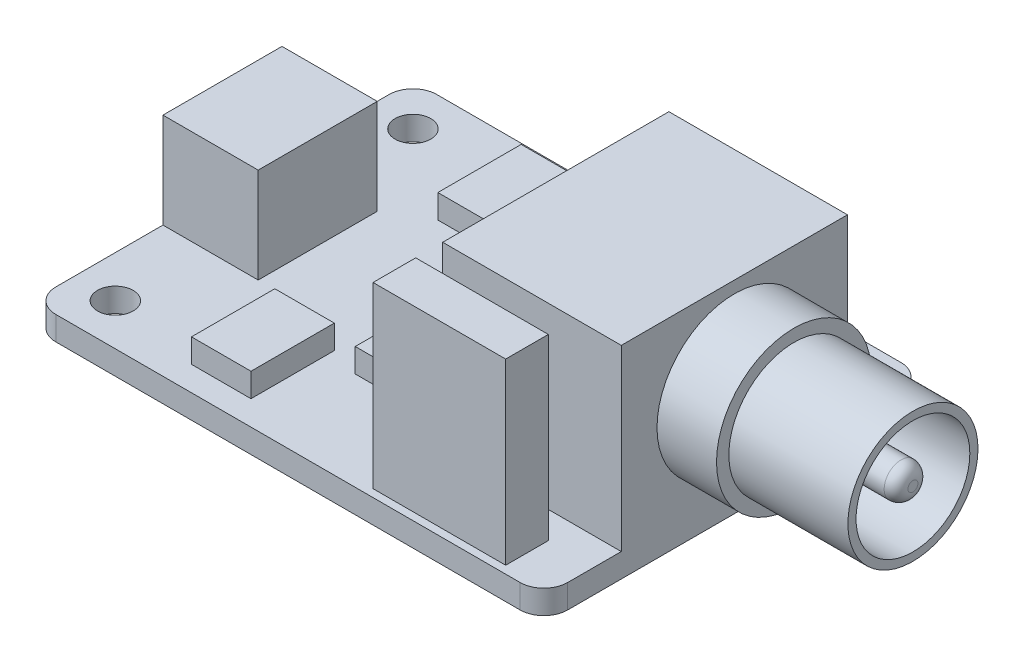
SolidWorks part; units mm, degrees
ref_plane "Front Plane" through (0, 0, 0) normal (0, 0, 1) x (1, 0, 0)
ref_plane "Top Plane" through (0, 0, 0) normal (0, 1, 0) x (1, 0, 0)
ref_plane "Right Plane" through (0, 0, 0) normal (1, 0, 0) x (0, 0, -1)
sketch "Sketch1" plane through (0, 0, 0) normal (0, 1, 0) x (1, 0, 0)
  line L1 (-179.1905, 78.9286) -> (-136.1905, 78.9286)
  line L2 (-179.1905, 78.9286) -> (-179.1905, 46.9286)
  line L3 (-179.1905, 46.9286) -> (-136.1905, 46.9286)
  line L4 (-136.1905, 78.9286) -> (-136.1905, 46.9286)
  circle A0 centre (-175.6905, 75.4286) radius 1.5
  circle A1 centre (-175.6905, 50.4286) radius 1.5
  dimension "D3" = 3
  dimension "D4" = 3
  dimension "D7" = 3.5
  dimension "D8" = 3.5
  dimension "D9" = 3.5
  dimension "D10" = 3.5
  dimension "D1" = 43
  dimension "D2" = 32
extrude "Boss-Extrude1" add sketch "Sketch1" along normal blind 2
fillet "Fillet1" radius 2 4 edges at (-179.1905, 1, -78.9286) (-136.1905, 1, -78.9286) (-136.1905, 1, -46.9286) (-179.1905, 1, -46.9286)
sketch "Sketch2" plane through (0, 2, 0) normal (0, 1, 0) x (1, 0, 0)
  line L0 (-179.1905, 76.9286) -> (-179.1905, 48.9286) construction
  line L1 (-195.986, 57.9286) -> (-187.986, 57.9286)
  line L2 (-195.986, 57.9286) -> (-195.986, 67.9286)
  line L3 (-195.986, 67.9286) -> (-187.986, 67.9286)
  line L4 (-187.986, 57.9286) -> (-187.986, 67.9286)
  line L6 (-151.1905, 53.4286) -> (-136.1905, 53.4286)
  line L7 (-151.1905, 53.4286) -> (-151.1905, 72.4286)
  line L8 (-151.1905, 72.4286) -> (-136.1905, 72.4286)
  line L9 (-136.1905, 53.4286) -> (-136.1905, 72.4286)
  line L10 (-136.1905, 48.9286) -> (-136.1905, 76.9286) construction
  line L11 (-177.1905, 46.9286) -> (-138.1905, 46.9286) construction
  line L12 (-138.1905, 78.9286) -> (-177.1905, 78.9286) construction
  line L14 (-151.1905, 51.1605) -> (-140.0499, 51.1605)
  line L15 (-151.1905, 51.1605) -> (-151.1905, 47.5777)
  line L16 (-151.1905, 47.5777) -> (-140.0499, 47.5777)
  line L17 (-140.0499, 51.1605) -> (-140.0499, 47.5777)
  point P4 (-195.986, 62.9286)
  point P7 (-179.1905, 62.9286)
  line M14 (-136.1905, 48.9286) -> (-136.1905, 76.9286)
  dimension "D1" = 10
  dimension "D2" = 8
  dimension "D4" = 15
  dimension "D5" = 6.5
  dimension "D6" = 6.5
extrude "Boss-Extrude2" add sketch "Sketch2" along normal blind 15 contours L8 L7 L6 M14 | L17 L14 L15 L16 region at (-143.6905, 2, -62.9286) region at (-145.6202, 2, -49.3691)
sketch "Sketch3" plane through (0, 2, 0) normal (0, 1, 0) x (1, 0, 0)
  line L0 (-179.1905, 76.9286) -> (-179.1905, 48.9286) construction
  line L1 (-171.1905, 57.9286) -> (-179.1905, 57.9286)
  line L2 (-171.1905, 57.9286) -> (-171.1905, 67.9286)
  line L3 (-171.1905, 67.9286) -> (-179.1905, 67.9286)
  line L4 (-179.1905, 57.9286) -> (-179.1905, 67.9286)
  point P4 (-179.1905, 62.9286)
  point P7 (-179.1905, 62.9286)
  dimension "D1" = 8
  dimension "D2" = 10
extrude "Boss-Extrude3" add sketch "Sketch3" along normal blind 8
sketch "Sketch4" plane through (0, 2, 0) normal (0, 1, 0) x (1, 0, 0)
  line L1 (-155.2818, 71.9845) -> (-160.2818, 71.9845)
  line L2 (-155.2818, 71.9845) -> (-155.2818, 64.9845)
  line L3 (-155.2818, 64.9845) -> (-160.2818, 64.9845)
  line L4 (-160.2818, 71.9845) -> (-160.2818, 64.9845)
  line L5 (-155.2818, 62.1725) -> (-160.2818, 62.1725)
  line L6 (-155.2818, 62.1725) -> (-155.2818, 55.1725)
  line L7 (-155.2818, 55.1725) -> (-160.2818, 55.1725)
  line L8 (-160.2818, 62.1725) -> (-160.2818, 55.1725)
  line L9 (-163.0126, 76.8418) -> (-168.0126, 76.8418)
  line L10 (-163.0126, 76.8418) -> (-163.0126, 69.8418)
  line L11 (-163.0126, 69.8418) -> (-168.0126, 69.8418)
  line L12 (-168.0126, 76.8418) -> (-168.0126, 69.8418)
  line L13 (-162.8613, 55.9959) -> (-167.8613, 55.9959)
  line L14 (-162.8613, 55.9959) -> (-162.8613, 48.9959)
  line L15 (-162.8613, 48.9959) -> (-167.8613, 48.9959)
  line L16 (-167.8613, 55.9959) -> (-167.8613, 48.9959)
  dimension "D1" = 5
  dimension "D2" = 7
  dimension "D3" = 5
  dimension "D4" = 7
  dimension "D5" = 5
  dimension "D6" = 7
  dimension "D7" = 5
  dimension "D8" = 7
extrude "Boss-Extrude4" add sketch "Sketch4" along normal blind 2
sketch "Sketch5" plane through (-179.1905, 0, 0) normal (-1, 0, 0) x (0, 0, 1)
  line L0 (-67.9286, 10) -> (-57.9286, 10) construction
  line L1 (-66.9286, 9) -> (-58.9286, 9)
  line L2 (-66.9286, 9) -> (-66.9286, 3)
  line L3 (-66.9286, 3) -> (-58.9286, 3)
  line L4 (-58.9286, 9) -> (-58.9286, 3)
  line L5 (-57.9286, 10) -> (-57.9286, 2) construction
  line L6 (-67.9286, 2) -> (-76.9286, 2) construction
  line L7 (-67.9286, 10) -> (-67.9286, 2) construction
  line L9 (-65.7286, 6.5) -> (-64.7286, 6.5)
  line L10 (-65.7286, 6.5) -> (-65.7286, 5.5)
  line L11 (-65.7286, 5.5) -> (-64.7286, 5.5)
  line L12 (-64.7286, 6.5) -> (-64.7286, 5.5)
  line L13 (-63.4286, 6.5) -> (-62.4286, 6.5)
  line L14 (-63.4286, 6.5) -> (-63.4286, 5.5)
  line L15 (-63.4286, 5.5) -> (-62.4286, 5.5)
  line L16 (-62.4286, 6.5) -> (-62.4286, 5.5)
  line L17 (-61.1286, 6.5) -> (-60.1286, 6.5)
  line L18 (-61.1286, 6.5) -> (-61.1286, 5.5)
  line L19 (-61.1286, 5.5) -> (-60.1286, 5.5)
  line L20 (-60.1286, 6.5) -> (-60.1286, 5.5)
  point P24 (-65.2286, 6.5)
  dimension "D1" = 1
  dimension "D2" = 1
  dimension "D3" = 1
  dimension "D4" = 1
  dimension "D5" = 1
  dimension "D6" = 1
  dimension "D7" = 1
  dimension "D8" = 1
  dimension "D9" = 1
  dimension "D10" = 1
  dimension "D11" = 2.5
  dimension "D12" = 2.5
  dimension "D13" = 2.5
  dimension "D14" = 1.2
  dimension "D15" = 1.2
  dimension "D16" = 1.3
extrude "Cut-Extrude1" cut sketch "Sketch5" against normal blind 7
draft "Draft1" type of draft neutral plane draft angle 1 faces to draft 3 face at (-179.1905, 6, -65.2286) face at (-179.1905, 6, -60.6286) face at (-179.1905, 6, -62.9286) neutral plane through (-172.1905, 6.5, -63.4286) neutral plane normal (0, 1, 0) parameters "D1"=1
chamfer "Chamfer1" distance 2.5 angle 8 12 edges at (-179.2079, 5.5, -60.6286) (-179.1992, 6, -60.1286) (-179.1905, 6.5, -60.6286) (-179.1992, 6, -61.1286) (-179.2079, 5.5, -62.9286) (-179.1992, 6, -62.4286) (-179.1905, 6.5, -62.9286) (-179.1992, 6, -63.4286) (-179.1992, 6, -65.7286) (-179.2079, 5.5, -65.2286) (-179.1992, 6, -64.7286) (-179.1905, 6.5, -65.2286) first distance on face at (-175.6992, 5.5, -60.6286) first distance on face at (-175.6948, 6, -60.1286) first distance on face at (-175.6905, 6.5, -60.6286) first distance on face at (-175.6948, 6, -61.1286) first distance on face at (-175.6992, 5.5, -62.9286) first distance on face at (-175.6948, 6, -62.4286) first distance on face at (-175.6905, 6.5, -62.9286) first distance on face at (-175.6948, 6, -63.4286) first distance on face at (-175.6948, 6, -65.7286) first distance on face at (-175.6992, 5.5, -65.2286) first distance on face at (-175.6948, 6, -64.7286) first distance on face at (-175.6905, 6.5, -65.2286)
sketch "Sketch6" plane through (-136.1905, 0, 0) normal (1, 0, 0) x (0, 0, -1)
  line L0 (53.4286, 17) -> (72.4286, 17) construction
  circle A0 centre (62.9286, 9.5) radius 6.5
  point P6 (62.9286, 17)
  dimension "D1" = 13
  dimension "D2" = 7.5
extrude "Boss-Extrude5" add sketch "Sketch6" along normal blind 5
sketch "Sketch7" plane through (-131.1905, 0, 0) normal (1, 0, 0) x (0, 0, -1)
  circle A0 centre (62.9286, 9.5) radius 5.4647
  circle A1 centre (62.9286, 9.5) radius 6.5 construction
  dimension "D1" = 0
extrude "Boss-Extrude6" add sketch "Sketch7" along normal blind 10
sketch "Sketch8" plane through (-121.1905, 0, 0) normal (1, 0, 0) x (0, 0, -1)
  circle A0 centre (62.9286, 9.5) radius 4.7788
  circle A1 centre (62.9286, 9.5) radius 1.4184
extrude "Cut-Extrude2" cut sketch "Sketch8" against normal blind 15
fillet "Fillet3" radius 1 1 edges at (-121.1905, 9.5, -64.347)
